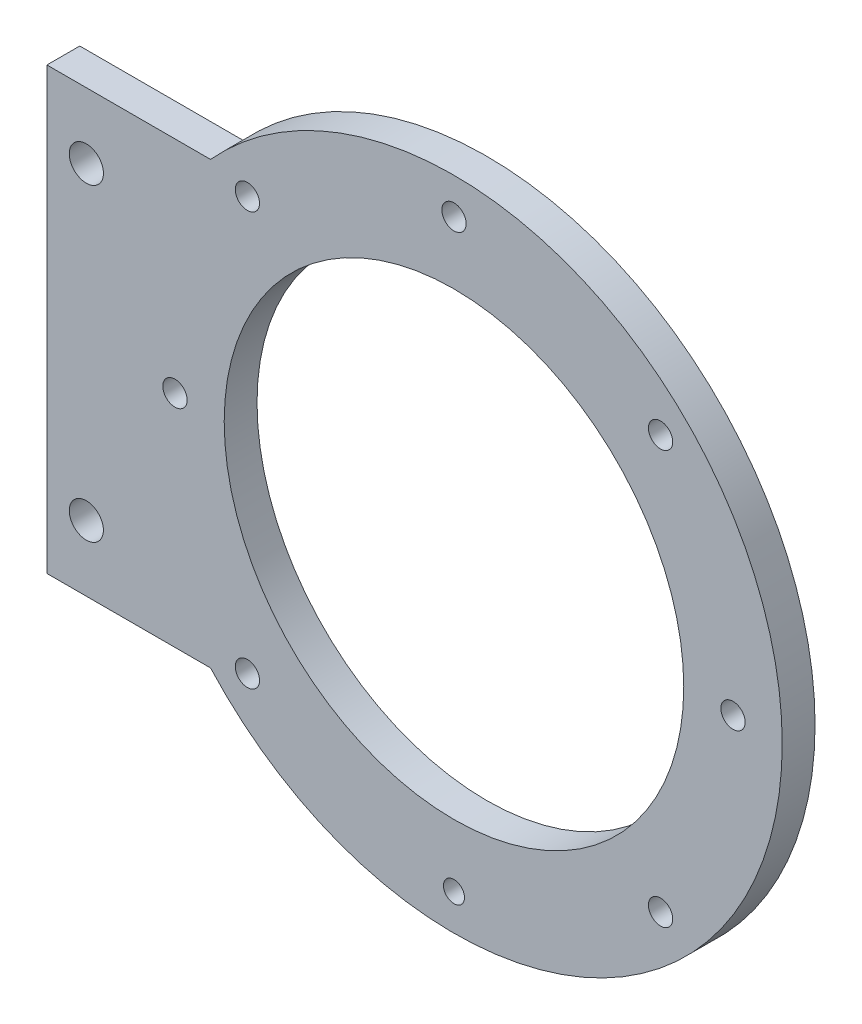
SolidWorks part; units mm, degrees
ref_plane "前视基准面" through (0, 0, 0) normal (0, 0, 1) x (1, 0, 0)
ref_plane "上视基准面" through (0, 0, 0) normal (0, 1, 0) x (1, 0, 0)
ref_plane "右视基准面" through (0, 0, 0) normal (1, 0, 0) x (0, 0, -1)
other "Configuration Table"
sketch "草图1" plane through (0, 0, 0) normal (0, 0, 1) x (1, 0, 0)
  line L0 (0, -67.082) -> (0, 0)
  line L1 (0, -67.082) -> (-12, -67.082)
  line L2 (-12, -67.082) -> (-12, 0)
  line L3 (0, 0) -> (-12, 0)
  line L4 (-12, -33.541) -> (95.5454, -33.541) construction
  line L5 (0, 0) -> (20, 0)
  line L6 (0, 0) -> (0, -67.082)
  line L7 (0, -67.082) -> (20, -67.082)
  line L8 (20, 0) -> (20, -67.082)
  circle A0 centre (-6, -57.082) radius 2.6
  circle A1 centre (-6, -10) radius 2.6
  circle A2 centre (50, -33.541) radius 50
  dimension "D1" = 5.2
  dimension "D2" = 6
  dimension "D5" = 6
  dimension "D6" = 10
  dimension "D8" = 6
  dimension "D9" = 5.2
  dimension "D10" = 10
  dimension "D12" = 100
  dimension "D3" = 12
  dimension "D4" = 67.082
  dimension "D7" = 12
  dimension "D11" = 20
  dimension "D13" = 50
extrude "凸台-拉伸1" add sketch "草图1" along normal blind 5 contours A2 L4 L8 L5 | L7 A2 L5 L8 | L4 A2 L7 L8 | A2 L0 L7 | L4 L2 L1 L0 A0 | L2 L4 L6 L3 A1 | A2 L5 L6 region at (-6, -49.9344, 0) region at (3.7716, -58.9289, 0) region at (-6, -17.1476, 0) region at (11.5844, -18.9627, 0) region at (3.7716, -8.1531, 0) region at (11.5844, -48.1194, 0) region at (16.4595, -68.4081, 0)
sketch "草图2" plane through (0, 0, 5) normal (0, 0, 1) x (1, 0, 0)
  line L3 (12.919, 0) -> (-12, 0)
  line L4 (-12, 0) -> (-12, -67.082)
  line L5 (-12, -67.082) -> (12.919, -67.082)
  line L6 (12.919, 0) -> (-12, 0)
  line L7 (-12, 0) -> (-12, -67.082)
  line L8 (-12, -67.082) -> (12.919, -67.082)
  arc A1 (12.919, -67.082) -> (12.919, 0) centre (50, -33.541) ccw
  arc A2 (12.919, -67.082) -> (12.919, 0) centre (50, -33.541) ccw
  circle A5 centre (92.5, -33.541) radius 1.85
  circle A16 centre (80.052, -63.5931) radius 1.85
  circle A17 centre (50, -76.041) radius 1.85
  circle A18 centre (19.948, -63.5931) radius 1.85
  circle A19 centre (7.5, -33.541) radius 1.85
  circle A20 centre (19.948, -3.489) radius 1.85
  circle A21 centre (50, 8.959) radius 1.85
  circle A22 centre (80.052, -3.489) radius 1.85
  point P18 (50, -33.541)
  point P25 (50, -33.541)
  dimension "D2" = 8
  dimension "D6" = 3.7
  dimension "D5" = 42.5
  dimension "D1" = 0
extrude "切除-拉伸1" cut sketch "草图2" against normal through all contours A5 | A19
sketch "草图3" plane through (0, 0, 5) normal (0, 0, 1) x (1, 0, 0)
  line L3 (12.919, 0) -> (-12, 0)
  line L4 (-12, 0) -> (-12, -67.082)
  line L5 (-12, -67.082) -> (12.919, -67.082)
  line L6 (12.919, 0) -> (-12, 0)
  line L7 (-12, 0) -> (-12, -67.082)
  line L8 (-12, -67.082) -> (12.919, -67.082)
  circle A0 centre (50, -33.541) radius 35
  arc A1 (12.919, -67.082) -> (12.919, 0) centre (50, -33.541) ccw
  arc A2 (12.919, -67.082) -> (12.919, 0) centre (50, -33.541) ccw
  dimension "D2" = 70
  dimension "D1" = 0
extrude "切除-拉伸2" cut sketch "草图3" against normal through all contours A0
sketch "草图4" plane through (0, 0, 5) normal (0, 0, 1) x (1, 0, 0)
  line L3 (12.919, 0) -> (-12, 0)
  line L4 (-12, 0) -> (-12, -67.082)
  line L5 (-12, -67.082) -> (12.919, -67.082)
  line L6 (12.919, 0) -> (-12, 0)
  line L7 (-12, 0) -> (-12, -67.082)
  line L8 (-12, -67.082) -> (12.919, -67.082)
  circle A0 centre (50, 10.959) radius 1.85
  arc A1 (12.919, -67.082) -> (12.919, 0) centre (50, -33.541) ccw
  arc A2 (12.919, -67.082) -> (12.919, 0) centre (50, -33.541) ccw
  circle A3 centre (81.4663, -2.0748) radius 1.85
  circle A4 centre (50, -78.041) radius 1.6
  circle A5 centre (94.5, -33.541) radius 1.85
  circle A6 centre (81.4663, -65.0073) radius 1.85
  circle A7 centre (50, -78.041) radius 1.85
  circle A8 centre (18.5337, -65.0073) radius 1.85
  circle A9 centre (5.5, -33.541) radius 1.85
  circle A10 centre (18.5337, -2.0748) radius 1.85
  point P26 (50, -33.541)
  point P28 (50, -33.541)
  dimension "D2" = 3.7
  dimension "D4" = 3.2
  dimension "D5" = 44.5
  dimension "D3" = 44.5
  dimension "D1" = 0
  dimension "D6" = 8
extrude "切除-拉伸3" cut sketch "草图4" against normal blind 10 contours A0 | A4 | A10 | A3 | A8 | A6
sketch "草图5" plane through (0, 0, 5) normal (0, 0, 1) x (1, 0, 0)
  circle A1 centre (-6, -10) radius 2.6
  circle A2 centre (-6, -10) radius 2.6
  circle A3 centre (-6, -57.082) radius 2.6
  circle A4 centre (-6, -57.082) radius 2.6
  circle A5 centre (7.5, -33.541) radius 1.85
  circle A6 centre (7.5, -33.541) radius 1.85
  circle A7 centre (92.5, -33.541) radius 1.85
  circle A8 centre (92.5, -33.541) radius 1.85
  circle A9 centre (50, -33.541) radius 35
  circle A10 centre (50, -33.541) radius 35
  circle A11 centre (18.5337, -65.0073) radius 1.85
  circle A12 centre (18.5337, -65.0073) radius 1.85
  circle A13 centre (81.4663, -2.0748) radius 1.85
  circle A14 centre (81.4663, -2.0748) radius 1.85
  circle A15 centre (18.5337, -2.0748) radius 1.85
  circle A16 centre (18.5337, -2.0748) radius 1.85
  circle A17 centre (50, -78.041) radius 1.6
  circle A18 centre (50, -78.041) radius 1.6
  circle A19 centre (81.4663, -65.0073) radius 1.85
  circle A20 centre (81.4663, -65.0073) radius 1.85
  circle A21 centre (50, 10.959) radius 1.85
  circle A22 centre (50, 10.959) radius 1.85
  dimension "D1" = 0
  dimension "D2" = 0
  dimension "D3" = 0
  dimension "D4" = 0
  dimension "D5" = 0
  dimension "D6" = 0
  dimension "D7" = 0
  dimension "D8" = 0
  dimension "D9" = 0
  dimension "D10" = 0
  dimension "D11" = 0
